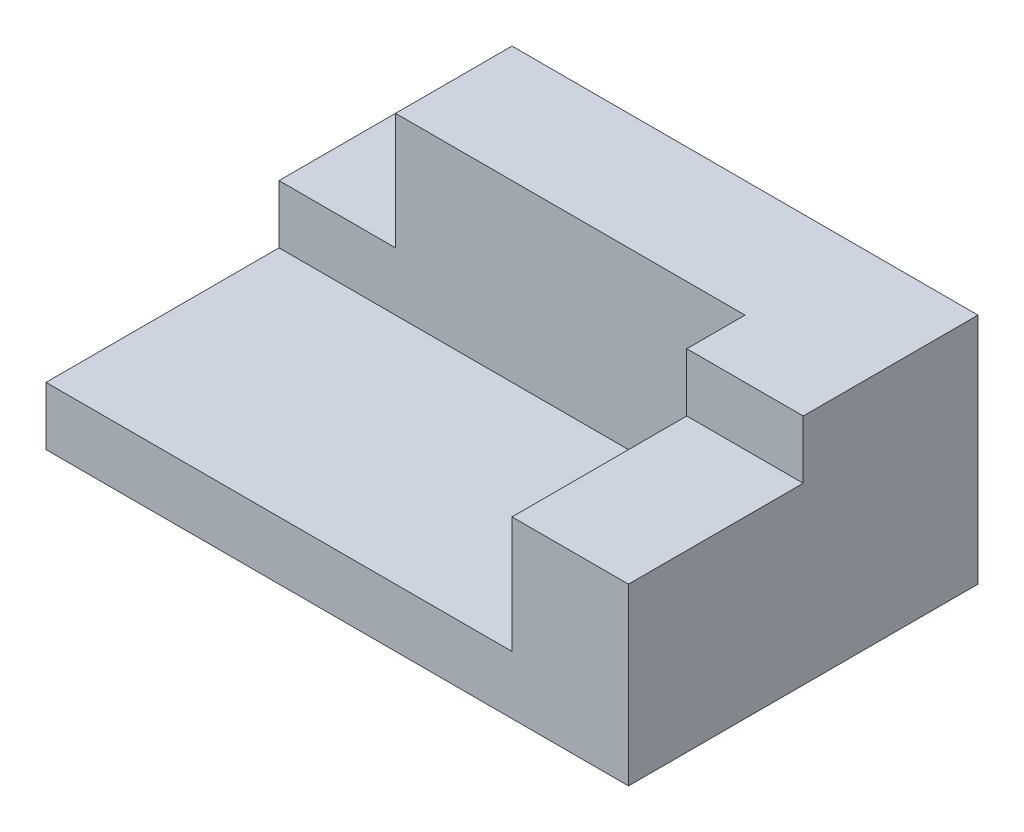
SolidWorks part; units mm, degrees
ref_plane "Alzado" through (0, 0, 0) normal (0, 0, 1) x (1, 0, 0)
ref_plane "Planta" through (0, 0, 0) normal (0, 1, 0) x (1, 0, 0)
ref_plane "Vista lateral" through (0, 0, 0) normal (1, 0, 0) x (0, 0, -1)
sketch "Croquis1" plane through (0, 0, 0) normal (0, 1, 0) x (1, 0, 0)
  line L1 (-50, 30) -> (50, 30)
  line L2 (-50, 30) -> (-50, -30)
  line L3 (-50, -30) -> (50, -30)
  line L4 (50, 30) -> (50, -30)
  line L5 (-50, 30) -> (50, -30) construction
  line L6 (-50, -30) -> (50, 30) construction
  line L7 (-50, 30) -> (-30, 30)
  line L8 (-50, 30) -> (-50, 10)
  line L9 (-50, 10) -> (-30, 10)
  line L10 (-30, 30) -> (-30, 10)
  line L11 (50, -30) -> (30, -30)
  line L12 (50, -30) -> (50, 0)
  line L13 (50, 0) -> (30, 0)
  line L14 (30, -30) -> (30, 0)
  line L15 (50, 0) -> (30, 0)
  line L16 (50, 0) -> (50, 30)
  line L17 (50, 30) -> (30, 30)
  line L18 (30, 0) -> (30, 10)
  line L19 (-30, 30) -> (30, 30)
  line L20 (-30, 30) -> (-30, 10)
  line L21 (-30, 10) -> (30, 10)
  point P0 (0, 0)
  dimension "D1" = 100
  dimension "D2" = 60
  dimension "D3" = 20
  dimension "D4" = 60
  dimension "D5" = 20
  dimension "D6" = 30
  dimension "D7" = 10
extrude "Saliente-Extruir1" add sketch "Croquis1" along normal blind 10 contours L21 L9 L2 L3 L14 L18 region at (-10, 0, 10)
extrude "Saliente-Extruir2" add sketch "Croquis1<3>" along normal blind 30 contours L14 L3 L4 L13 region at (40, 0, 15)
sketch "Croquis1<3>" plane through (0, 0, 0) normal (0, 1, 0) x (1, 0, 0) same geometry as "Croquis1"
extrude "Saliente-Extruir3" add sketch "Croquis1<4>" along normal blind 40 contours L10 L21 L18 L13 L4 L1 region at (13.3333, 0, -18.3333)
sketch "Croquis1<4>" plane through (0, 0, 0) normal (0, 1, 0) x (1, 0, 0) same geometry as "Croquis1"
extrude "Saliente-Extruir4" add sketch "Croquis1<5>" along normal blind 20 contours L10 L1 L2 L9 region at (-40, 0, -20)
sketch "Croquis1<5>" plane through (0, 0, 0) normal (0, 1, 0) x (1, 0, 0) same geometry as "Croquis1"
